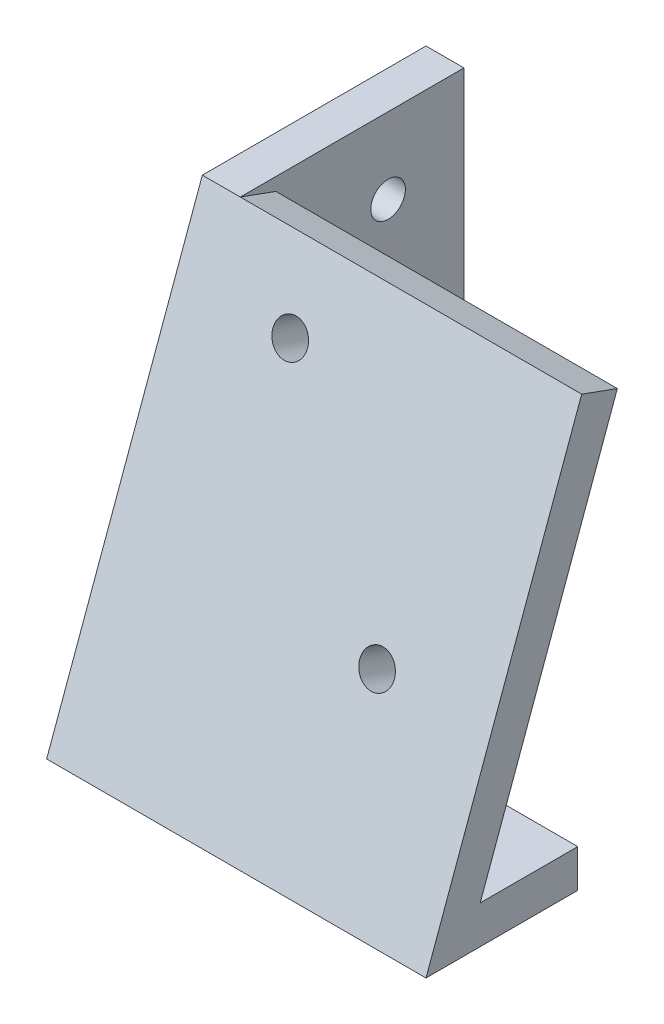
SolidWorks part; units mm, degrees
material "ABS"
ref_plane "Front Plane" through (0, 0, 0) normal (0, 0, 1) x (1, 0, 0)
ref_plane "Top Plane" through (0, 0, 0) normal (0, 1, 0) x (1, 0, 0)
ref_plane "Right Plane" through (0, 0, 0) normal (1, 0, 0) x (0, 0, -1)
sketch "Sketch1" plane through (0, 0, 0) normal (1, 0, 0) x (0, 0, -1)
  line L0 (0, 0) -> (-50, 0)
  line L1 (-50, 0) -> (-29.4788, 56.3816)
  line L2 (-29.4788, 56.3816) -> (-24.7803, 54.6715)
  line L3 (-24.7803, 54.6715) -> (-42.8593, 5)
  line L4 (-42.8593, 5) -> (0, 5)
  line L5 (0, 5) -> (0, 0)
  dimension "D1" = 60
  dimension "D2" = 50
  dimension "D3" = 70
  dimension "D4" = 5
  dimension "D5" = 5
extrude "Main" add sketch "Sketch1" along normal mid plane 50
sketch "Sketch2" plane through (0, 0, 0) normal (0, 0, -1) x (-1, 0, 0)
  line L0 (-25, 56.3816) -> (25, 56.3816) construction
  line L1 (-25, 0) -> (-20, 0)
  line L2 (-25, 0) -> (-25, 56.3816)
  line L3 (-25, 56.3816) -> (-20, 56.3816)
  line L4 (-20, 0) -> (-20, 56.3816)
  dimension "D1" = 5
extrude "Back" add sketch "Sketch2" against normal up to next
hole_wizard "Base Holes" positions "3DSketch4" profile "Sketch5" hole size "#8" standard "ANSI Inch"
sketch3d "3DSketch4"
  line L0 (-25, 5, 0) -> (-25, 5, 42.8593) construction
  line L4 (20, 5, 42.8593) -> (-25, 5, 42.8593) construction
  point P0 (10, 5, 32.6993)
  point P2 (-10, 5, 32.6993)
  dimension "D1" = 15
  dimension "D2" = 15
  dimension "D3" = 10.16
  dimension "D4" = 10.16
sketch "Sketch5" plane through (10, 5, 32.6993) normal (1, 0, 0) x (0, 0, 1)
  line L0 (0, 0) -> (0, 5)
  line L1 (0, 5) -> (2.286, 5)
  line L2 (2.286, 5) -> (2.286, 0)
  line L5 (2.286, 0) -> (0, 0)
  line L10 (0, 5) -> (-2.286, 5) construction
  line L11 (0, -6.35) -> (0, 107.95) construction
  dimension "Hole Dia." = 4.572
  dimension "Hole Depth" = 5
  dimension "Drill Angle" = 180
hole_wizard "BackPanelHoles" positions "Sketch6" profile "Sketch7" hole size "#8" standard "ANSI Inch"
sketch "Sketch6" plane through (20, 0, 0) normal (-1, 0, 0) x (0, 0, 1)
  line L0 (29.4788, 56.3816) -> (0, 56.3816) construction
  line L1 (0, 5) -> (0, 56.3816) construction
  line L2 (50, 0) -> (0, 0) construction
  point P0 (10, 46.3816)
  point P2 (25, 20)
  dimension "D1" = 10
  dimension "D2" = 10
  dimension "D3" = 20
  dimension "D4" = 25
sketch "Sketch7" plane through (20, 46.3816, 10) normal (0, 1, 0) x (0, 0, 1)
  line L0 (0, 0) -> (0, 5)
  line L1 (0, 5) -> (2.286, 5)
  line L2 (2.286, 5) -> (2.286, 0)
  line L5 (2.286, 0) -> (0, 0)
  line L10 (0, 5) -> (-2.286, 5) construction
  line L11 (0, -6.35) -> (0, 107.95) construction
  dimension "Hole Dia." = 4.572
  dimension "Hole Depth" = 5
  dimension "Drill Angle" = 180
hole_wizard "#8 (0.18) Diameter Hole3" positions "3DSketch5" profile "Sketch8" hole size "#8" standard "ANSI Inch"
sketch3d "3DSketch5"
  line L1 (20, 56.3816, 29.4788) -> (-25, 56.3816, 29.4788) construction
  line L2 (25, 0, 50) -> (-25, 0, 50) construction
  line L3 (-25, 56.3816, 29.4788) -> (-25, 0, 50) construction
  line L4 (25, 56.3816, 29.4788) -> (25, 0, 50) construction
  point P0 (-10, 46.9846, 32.899)
  point P2 (10, 23.4923, 41.4495)
  dimension "D1" = 15
  dimension "D2" = 10
  dimension "D3" = 25
  dimension "D4" = 15
sketch "Sketch8" plane through (-10, 46.9846, 32.899) normal (1, 0, 0) x (0, -0.9397, 0.342)
  line L0 (0, 0) -> (0, 5)
  line L1 (0, 5) -> (2.286, 5)
  line L2 (2.286, 5) -> (2.286, 0)
  line L5 (2.286, 0) -> (0, 0)
  line L10 (0, 5) -> (-2.286, 5) construction
  line L11 (0, -6.35) -> (0, 107.95) construction
  dimension "Hole Dia." = 4.572
  dimension "Hole Depth" = 5
  dimension "Drill Angle" = 180
ref_plane "Midplane" through (0, 0, 0) normal (-1, 0, 0) x (0, 0, 1)
mirror "Mirror1" about plane through (0, 0, 0) normal (-1, 0, 0) of "BackPanelHoles", "Back"
sketch "Sketch9" plane through (20, 0, 0) normal (-1, 0, 0) x (0, 0, 1)
  line L0 (29.4788, 56.3816) -> (0, 56.3816)
  line L1 (0, 56.3816) -> (0, 5)
  line L2 (0, 5) -> (42.8593, 5)
  line L3 (42.8593, 5) -> (24.7803, 54.6715)
  line L4 (24.7803, 54.6715) -> (29.4788, 56.3816)
extrude "Mirror Cut" cut sketch "Sketch9" against normal up to next
sketch "Sketch10" plane through (0, 5, 0) normal (0, 1, 0) x (1, 0, 0)
  line L0 (25, -42.8593) -> (25, 0) construction
  line L1 (-20, 0) -> (25, 0)
  line L2 (-20, 0) -> (-20, -30)
  line L3 (-20, -30) -> (25, -30)
  line L4 (25, 0) -> (25, -30)
  dimension "D1" = 30
extrude "BatteryCut" cut sketch "Sketch10" against normal up to next
